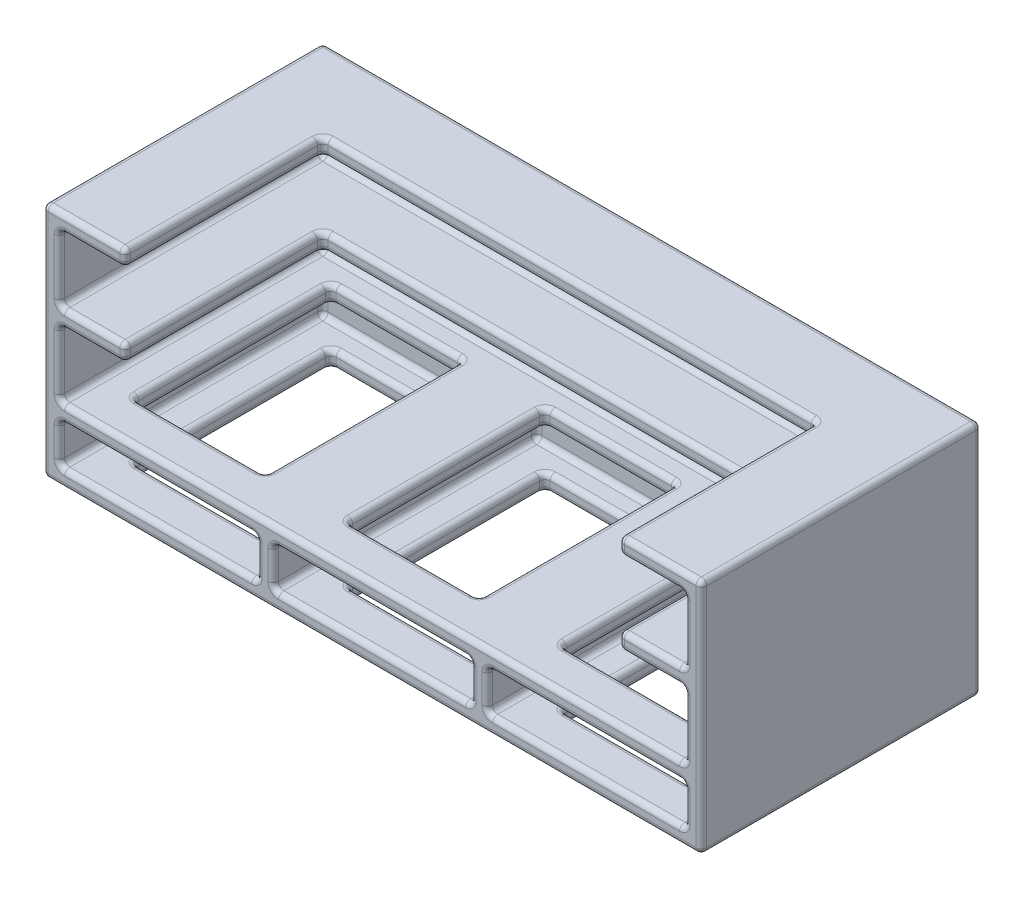
SolidWorks part; units mm, degrees
ref_plane "Front Plane" through (0, 0, 0) normal (0, 0, 1) x (1, 0, 0)
ref_plane "Top Plane" through (0, 0, 0) normal (0, 1, 0) x (1, 0, 0)
ref_plane "Right Plane" through (0, 0, 0) normal (1, 0, 0) x (0, 0, -1)
sketch "Sketch1" plane through (0, 0, 0) normal (0, 0, 1) x (1, 0, 0)
  line L1 (0, 0) -> (-127, 0)
  line L2 (0, 0) -> (0, 45.72)
  line L3 (0, 45.72) -> (-127, 45.72)
  line L4 (-127, 0) -> (-127, 45.72)
  line L5 (-123.825, 42.545) -> (-3.175, 42.545)
  line L6 (-123.825, 42.545) -> (-123.825, 29.845)
  line L7 (-123.825, 29.845) -> (-3.175, 29.845)
  line L8 (-3.175, 42.545) -> (-3.175, 29.845)
  line L9 (-123.825, 26.67) -> (-3.175, 26.67)
  line L10 (-123.825, 26.67) -> (-123.825, 13.97)
  line L11 (-123.825, 13.97) -> (-3.175, 13.97)
  line L12 (-3.175, 26.67) -> (-3.175, 13.97)
  line L13 (-123.825, 10.795) -> (-85.725, 10.795)
  line L14 (-123.825, 10.795) -> (-123.825, 3.175)
  line L15 (-123.825, 3.175) -> (-85.725, 3.175)
  line L16 (-85.725, 10.795) -> (-85.725, 3.175)
  line L17 (-82.55, 10.795) -> (-44.45, 10.795)
  line L18 (-82.55, 10.795) -> (-82.55, 3.175)
  line L19 (-82.55, 3.175) -> (-44.45, 3.175)
  line L20 (-44.45, 10.795) -> (-44.45, 3.175)
  line L21 (-41.275, 10.795) -> (-3.175, 10.795)
  line L22 (-41.275, 10.795) -> (-41.275, 3.175)
  line L23 (-41.275, 3.175) -> (-3.175, 3.175)
  line L24 (-3.175, 10.795) -> (-3.175, 3.175)
  point P25 (-123.825, 6.985)
  point P26 (-82.55, 6.985)
  dimension "D1" = 120.65
  dimension "D2" = 3.175
  dimension "D3" = 3.175
  dimension "D4" = 12.7
  dimension "D5" = 12.7
  dimension "D6" = 3.175
  dimension "D7" = 3.175
  dimension "D8" = 3.175
  dimension "D9" = 7.62
  dimension "D10" = 38.1
  dimension "D11" = 38.1
  dimension "D12" = 38.1
  dimension "D13" = 3.175
  dimension "D14" = 3.175
  dimension "D15" = 3.175
  dimension "D16" = 3.175
extrude "Boss-Extrude1" add sketch "Sketch1" along normal blind 50.8
sketch "Sketch2" plane through (0, 0, 0) normal (0, 0, -1) x (-1, 0, 0)
  line L1 (0, 0) -> (127, 0)
  line L2 (0, 0) -> (0, 45.72)
  line L3 (0, 45.72) -> (127, 45.72)
  line L4 (127, 0) -> (127, 45.72)
extrude "Boss-Extrude2" add sketch "Sketch2" along normal blind 3.175
sketch "Sketch3" plane through (0, 0, 50.8) normal (0, 0, 1) x (1, 0, 0)
  line L0 (0, 45.72) -> (-127, 45.72) construction
  line L1 (-15.875, 45.72) -> (-111.125, 45.72)
  line L2 (-15.875, 45.72) -> (-15.875, 13.97)
  line L3 (-15.875, 13.97) -> (-111.125, 13.97)
  line L4 (-111.125, 45.72) -> (-111.125, 13.97)
  line L5 (-123.825, 13.97) -> (-3.175, 13.97) construction
  line L7 (-3.175, 13.97) -> (-3.175, 26.67) construction
  line L9 (-123.825, 26.67) -> (-123.825, 13.97) construction
  dimension "D1" = 12.7
  dimension "D2" = 12.7
extrude "Cut-Extrude1" cut sketch "Sketch3" against normal blind 38.1
sketch "Sketch4" plane through (0, 0, 0) normal (0, -1, 0) x (-1, 0, 0)
  line L1 (117.475, -42.8625) -> (92.075, -42.8625)
  line L2 (117.475, -42.8625) -> (117.475, -4.7625)
  line L3 (117.475, -4.7625) -> (92.075, -4.7625)
  line L4 (92.075, -42.8625) -> (92.075, -4.7625)
  line L5 (76.2, -42.8625) -> (50.8, -42.8625)
  line L6 (76.2, -42.8625) -> (76.2, -4.7625)
  line L7 (76.2, -4.7625) -> (50.8, -4.7625)
  line L8 (50.8, -42.8625) -> (50.8, -4.7625)
  line L9 (34.925, -42.8625) -> (9.525, -42.8625)
  line L10 (34.925, -42.8625) -> (34.925, -4.7625)
  line L11 (34.925, -4.7625) -> (9.525, -4.7625)
  line L12 (9.525, -42.8625) -> (9.525, -4.7625)
  line L13 (127, -50.8) -> (127, 3.175) construction
  line L14 (0, -50.8) -> (0, 3.175) construction
  line L15 (127, -50.8) -> (0, -50.8) construction
  dimension "D1" = 25.4
  dimension "D2" = 25.4
  dimension "D3" = 25.4
  dimension "D4" = 9.525
  dimension "D5" = 9.525
  dimension "D6" = 38.1
  dimension "D7" = 7.9375
  dimension "D8" = 15.875
extrude "Cut-Extrude2" cut sketch "Sketch4" against normal up to surface (13.97 mm away) up to face at (-63.5, 13.97, 25.4)
fillet "Fillet1" radius 1.016 168 edges at (-34.925, 0, 23.8125) (-22.225, 0, 4.7625) (-9.525, 0, 23.8125) (-22.225, 0, 42.8625) (-22.225, 13.97, 4.7625) (-9.525, 1.5875, 4.7625) (-9.525, 12.3825, 4.7625) (-9.525, 13.97, 23.8125) (-9.525, 1.5875, 42.8625) (-9.525, 12.3825, 42.8625) (-22.225, 13.97, 42.8625) (-34.925, 1.5875, 42.8625) (-34.925, 12.3825, 42.8625) (-34.925, 13.97, 23.8125) (-34.925, 1.5875, 4.7625) (-34.925, 12.3825, 4.7625) (-76.2, 0, 23.8125) (-63.5, 0, 4.7625) (-50.8, 0, 23.8125) (-63.5, 0, 42.8625) (-63.5, 13.97, 4.7625) (-50.8, 1.5875, 4.7625) (-50.8, 12.3825, 4.7625) (-50.8, 13.97, 23.8125) (-50.8, 1.5875, 42.8625) (-50.8, 12.3825, 42.8625) (-63.5, 13.97, 42.8625) (-76.2, 1.5875, 42.8625) (-76.2, 12.3825, 42.8625) (-76.2, 13.97, 23.8125) (-76.2, 1.5875, 4.7625) (-76.2, 12.3825, 4.7625) (-117.475, 0, 23.8125) (-104.775, 0, 4.7625) (-92.075, 0, 23.8125) (-104.775, 0, 42.8625) (-104.775, 13.97, 4.7625) (-92.075, 1.5875, 4.7625) (-92.075, 12.3825, 4.7625) (-92.075, 13.97, 23.8125) (-92.075, 1.5875, 42.8625) (-92.075, 12.3825, 42.8625) (-104.775, 13.97, 42.8625) (-117.475, 1.5875, 42.8625) (-117.475, 12.3825, 42.8625) (-117.475, 13.97, 23.8125) (-117.475, 1.5875, 4.7625) (-117.475, 12.3825, 4.7625) (-34.925, 3.175, 23.8125) (-22.225, 3.175, 42.8625) (-9.525, 3.175, 23.8125) (-22.225, 3.175, 4.7625) (-76.2, 3.175, 23.8125) (-63.5, 3.175, 42.8625) (-50.8, 3.175, 23.8125) (-63.5, 3.175, 4.7625) (-117.475, 3.175, 23.8125) (-104.775, 3.175, 42.8625) (-92.075, 3.175, 23.8125) (-104.775, 3.175, 4.7625) (-15.875, 44.1325, 50.8) (-15.875, 28.2575, 50.8) (-111.125, 28.2575, 50.8) (-111.125, 44.1325, 50.8) (-15.875, 44.1325, 12.7) (-15.875, 28.2575, 12.7) (-63.5, 45.72, 12.7) (-111.125, 28.2575, 12.7) (-111.125, 44.1325, 12.7) (-15.875, 45.72, 31.75) (-111.125, 45.72, 31.75) (-63.5, 42.545, 12.7) (-63.5, 29.845, 12.7) (-111.125, 42.545, 31.75) (-111.125, 29.845, 31.75) (-15.875, 42.545, 31.75) (-15.875, 29.845, 31.75) (0, 22.86, -3.175) (-63.5, 0, -3.175) (-127, 22.86, -3.175) (-63.5, 45.72, -3.175) (-41.275, 6.985, 0) (-22.225, 3.175, 0) (-3.175, 6.985, 0) (-22.225, 10.795, 0) (-41.275, 6.985, 50.8) (-22.225, 3.175, 50.8) (-3.175, 6.985, 50.8) (-22.225, 10.795, 50.8) (-41.275, 10.795, 25.4) (-3.175, 10.795, 25.4) (-3.175, 3.175, 25.4) (-41.275, 3.175, 25.4) (-82.55, 6.985, 0) (-63.5, 3.175, 0) (-44.45, 6.985, 0) (-63.5, 10.795, 0) (-82.55, 6.985, 50.8) (-63.5, 3.175, 50.8) (-44.45, 6.985, 50.8) (-63.5, 10.795, 50.8) (-82.55, 10.795, 25.4) (-44.45, 10.795, 25.4) (-44.45, 3.175, 25.4) (-82.55, 3.175, 25.4) (-123.825, 6.985, 0) (-104.775, 3.175, 0) (-85.725, 6.985, 0) (-104.775, 10.795, 0) (-123.825, 6.985, 50.8) (-104.775, 3.175, 50.8) (-85.725, 6.985, 50.8) (-104.775, 10.795, 50.8) (-123.825, 10.795, 25.4) (-85.725, 10.795, 25.4) (-85.725, 3.175, 25.4) (-123.825, 3.175, 25.4) (-123.825, 20.32, 0) (-63.5, 13.97, 0) (-3.175, 20.32, 0) (-63.5, 26.67, 0) (-123.825, 20.32, 50.8) (-63.5, 13.97, 50.8) (-3.175, 20.32, 50.8) (-117.475, 26.67, 50.8) (-9.525, 26.67, 50.8) (-123.825, 26.67, 25.4) (-3.175, 26.67, 25.4) (-3.175, 13.97, 25.4) (-123.825, 13.97, 25.4) (-123.825, 36.195, 0) (-63.5, 29.845, 0) (-3.175, 36.195, 0) (-63.5, 42.545, 0) (-123.825, 36.195, 50.8) (-9.525, 29.845, 50.8) (-117.475, 29.845, 50.8) (-3.175, 36.195, 50.8) (-117.475, 42.545, 50.8) (-9.525, 42.545, 50.8) (-123.825, 42.545, 25.4) (-3.175, 42.545, 25.4) (-3.175, 29.845, 25.4) (-123.825, 29.845, 25.4) (0, 22.86, 50.8) (-119.0625, 45.72, 50.8) (-7.9375, 45.72, 50.8) (-127, 22.86, 50.8) (-63.5, 0, 50.8) (0, 0, 23.8125) (-127, 0, 23.8125) (-127, 45.72, 23.8125) (0, 45.72, 23.8125) (-63.5, 26.67, 12.7) (-111.125, 26.67, 31.75) (-15.875, 26.67, 31.75) (-34.925, 10.795, 23.8125) (-22.225, 10.795, 42.8625) (-9.525, 10.795, 23.8125) (-22.225, 10.795, 4.7625) (-76.2, 10.795, 23.8125) (-63.5, 10.795, 42.8625) (-50.8, 10.795, 23.8125) (-63.5, 10.795, 4.7625) (-117.475, 10.795, 23.8125) (-104.775, 10.795, 42.8625) (-92.075, 10.795, 23.8125) (-104.775, 10.795, 4.7625)
